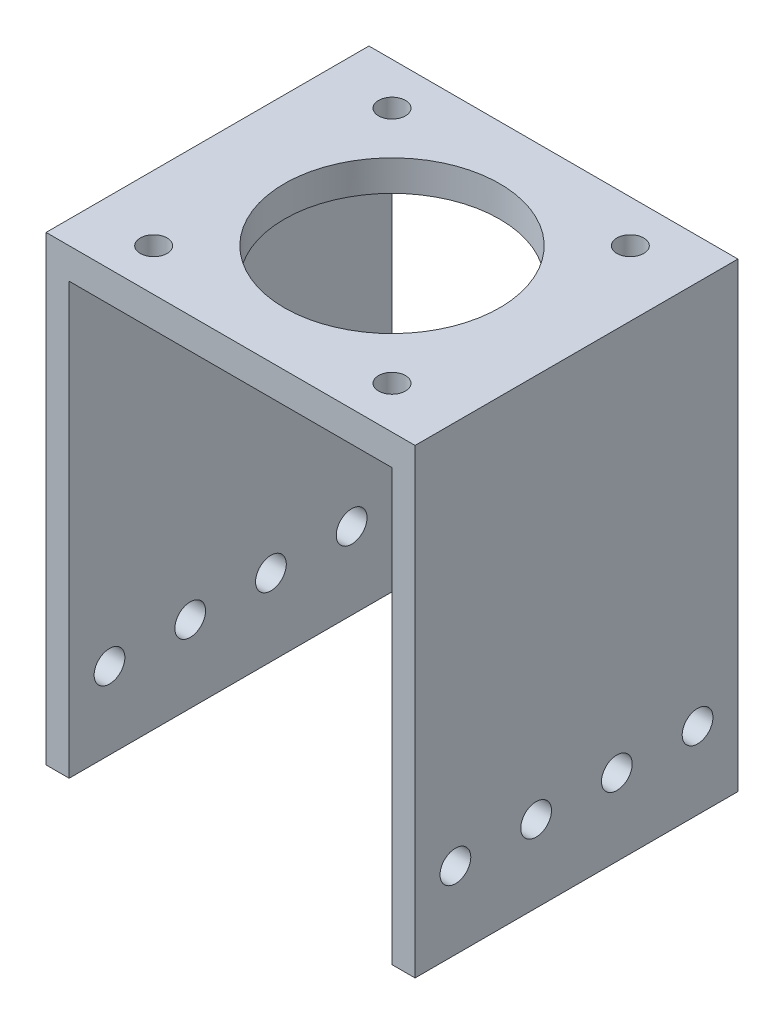
SolidWorks part; units mm, degrees
ref_plane "Front Plane" through (0, 0, 0) normal (0, 0, 1) x (1, 0, 0)
ref_plane "Top Plane" through (0, 0, 0) normal (0, 1, 0) x (1, 0, 0)
ref_plane "Right Plane" through (0, 0, 0) normal (1, 0, 0) x (0, 0, -1)
sketch "Sketch1" plane through (0, 0, 0) normal (0, 0, 1) x (1, 0, 0)
  line L0 (-21, -30) -> (-21, 26)
  line L1 (-24, -30) -> (-21, -30)
  line L2 (-24, -30) -> (-24, 30)
  line L3 (-24, 30) -> (24, 30)
  line L4 (24, -30) -> (24, 30)
  line L5 (-24, -30) -> (24, 30) construction
  line L6 (-24, 30) -> (24, -30) construction
  line L7 (-21, 26) -> (21, 26)
  line L8 (21, 26) -> (21, -30)
  line L9 (21, -30) -> (24, -30)
  point P0 (0, 0)
  dimension "D1" = 60
  dimension "D2" = 3
  dimension "D3" = 42
  dimension "D4" = 4
extrude "Boss-Extrude1" add sketch "Sketch1" along normal blind 42
sketch "Sketch2" plane through (0, 30, 0) normal (0, 1, 0) x (1, 0, 0)
  line L0 (24, -42) -> (-24, -42) construction
  line L1 (0, 0) -> (0, -42) construction
  line L2 (24, -42) -> (24, 0) construction
  line L3 (0, -21) -> (24, -21) construction
  line L4 (-15.5, -36.5) -> (15.5, -36.5) construction
  line L5 (15.5, -36.5) -> (15.5, -5.5) construction
  circle A0 centre (15.5, -36.5) radius 1.75
  circle A1 centre (15.5, -5.5) radius 1.75
  circle A2 centre (-15.5, -36.5) radius 1.75
  circle A3 centre (-15.5, -5.5) radius 1.75
  circle A4 centre (0, -21) radius 14
  dimension "D2" = 3.5
  dimension "D4" = 28
  dimension "D1" = 31
extrude "Cut-Extrude1" cut sketch "Sketch2" against normal through all
sketch "Sketch3" plane through (24, 0, 0) normal (1, 0, 0) x (0, 0, -1)
  line L0 (-21, 30) -> (-21, -30) construction
  line L1 (-42, 30) -> (0, 30) construction
  line L2 (-42, -30) -> (0, -30) construction
  line L3 (-10.5, -20) -> (0, -20) construction
  line L4 (-15.75, -18) -> (-5.25, -18) construction
  line L5 (-10.5, -20) -> (-21, -20) construction
  line L7 (0, -30) -> (0, 30) construction
  circle A2 centre (-15.75, -20) radius 2
  circle A3 centre (-5.25, -20) radius 2
  circle A4 centre (-36.75, -20) radius 2
  circle A5 centre (-26.25, -20) radius 2
  dimension "D1" = 4
  dimension "D2" = 10
extrude "Cut-Extrude2" cut sketch "Sketch3" against normal through all
